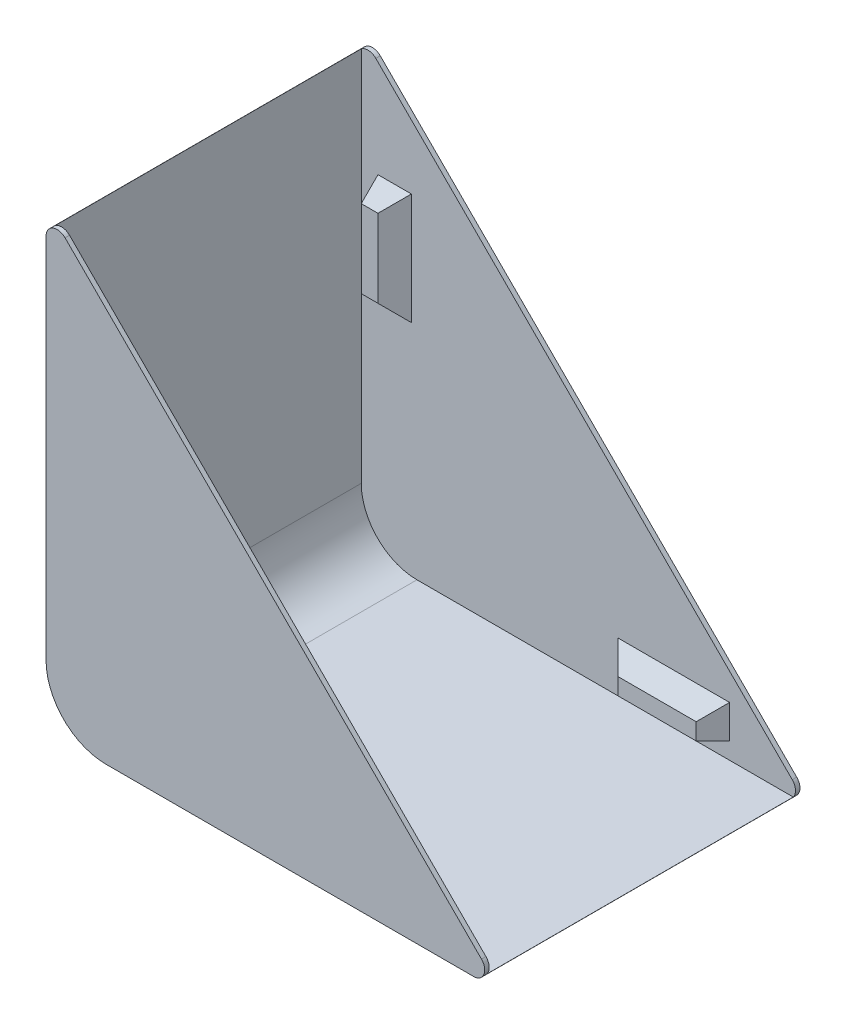
SolidWorks part; units mm, degrees
ref_plane "Plan de face" through (0, 0, 0) normal (0, 0, 1) x (1, 0, 0)
ref_plane "Plan de dessus" through (0, 0, 0) normal (0, 1, 0) x (1, 0, 0)
ref_plane "Plan de droite" through (0, 0, 0) normal (1, 0, 0) x (0, 0, -1)
sketch "Esquisse1" plane through (0, 0, 0) normal (0, 0, 1) x (1, 0, 0)
  line L0 (0, 0) -> (0, 80)
  line L1 (0, 80) -> (80, 0)
  line L2 (80, 0) -> (0, 0)
  dimension "D1" = 80
  dimension "D2" = 80
extrude "Boss.-Extru.1" add sketch "Esquisse1" along normal mid plane 55
sketch "Esquisse4" plane through (0, 0, 0) normal (1, 0, 0) x (0, 0, -1)
  line L0 (-61.9556, 0) -> (61.9556, 0) construction
  point P4 (0, 0)
fillet "Congé1" radius 10 1 edges at (0, 0, 0)
shell "Coque1" thickness 0.8 removed face at (40, 40, 0) outward yes
fillet "Congé2" radius 2 2 edges at (80.8, -0.8, 0) (-0.8, 80.8, 0)
sketch "Esquisse2" plane through (0, 0, 27.5) normal (0, 0, -1) x (-1, 0, 0)
  line L0 (-66.1349, 3) -> (-66.1349, 9)
  line L1 (-66.1349, 3) -> (-46.1349, 3)
  line L2 (-66.1349, 9) -> (-46.1349, 9)
  line L3 (-46.1349, 3) -> (-46.1349, 9)
  line L4 (-10, 0) -> (-77.5716, 0) construction
  line L5 (-3, 39.4964) -> (-3, 59.4964)
  line L6 (-3, 39.4964) -> (-9, 39.4964)
  line L7 (-3, 59.4964) -> (-9, 59.4964)
  line L8 (-9, 39.4964) -> (-9, 59.4964)
  line L9 (0, 77.5716) -> (0, 10) construction
  arc A0 (-77.3858, 2.6142) -> (-77.5716, 0) centre (-75.9716, 1.2) ccw construction
  dimension "D1" = 3
  dimension "D2" = 20
  dimension "D3" = 6
  dimension "D4" = 10
  dimension "D5" = 20
  dimension "D6" = 3
  dimension "D7" = 6
extrude "Boss.-Extru.2" add sketch "Esquisse2" along normal blind 3
chamfer "Chanfrein1" distance 3 6 edges at (56.1349, 9, 24.5) (66.1349, 6, 24.5) (46.1349, 6, 24.5) (6, 39.4964, 24.5) (6, 59.4964, 24.5) (9, 49.4964, 24.5)
mirror "Symétrie1" about plane through (0, 0, 0) normal (0, 0, 1) of "Chanfrein1", "Boss.-Extru.2"
equation "\"longueur\"=80"
equation "\"D1@Esquisse1\"=\"longueur\""
equation "\"D2@Esquisse1\"=\"longueur\""
equation "\"largeur_ext\"=10"
equation "\"D1@Boss.-Extru.1\"=\"largeur_int\""
equation "\"largeur_int\" = 55"
equation "\"conges\"=10"
equation "\"D1@Congé1\"=\"conges\""
equation "\"buse\"= 0.4'Buse impression"
equation "\"D1@Coque1\"=\"buse\"*2"
